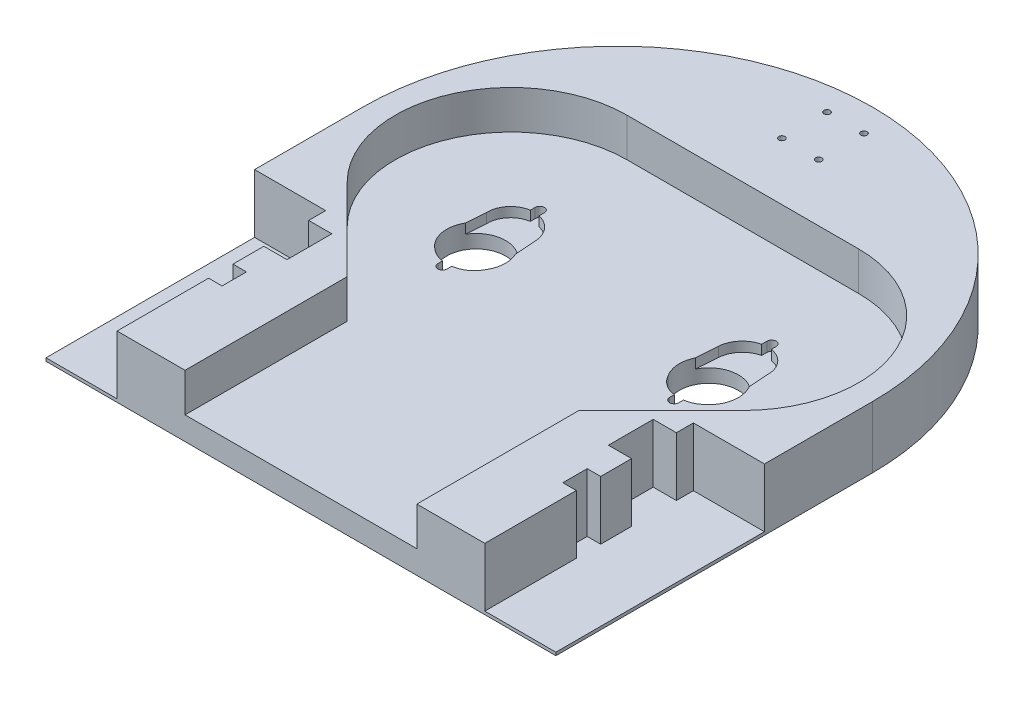
SolidWorks part; units mm, degrees
ref_plane "Plan de face" through (0, 0, 0) normal (0, 0, 1) x (1, 0, 0)
ref_plane "Plan de dessus" through (0, 0, 0) normal (0, 1, 0) x (1, 0, 0)
ref_plane "Plan de droite" through (0, 0, 0) normal (1, 0, 0) x (0, 0, -1)
sketch "Esquisse1" plane through (0, 0, 0) normal (0, 1, 0) x (1, 0, 0)
  line L0 (0, 0) -> (330, 0)
  line L1 (330, 0) -> (330, 370)
  line L2 (0, 0) -> (0, 370)
  line L3 (0, 370) -> (330, 370)
  dimension "D1" = 330
  dimension "D2" = 370
extrude "corp" add sketch "Esquisse1" along normal blind 40
fillet "congé avant" 2 edges at (0, 20, -370) (330, 20, -370) type full round first side face at (0, 20, -185) second side face at (330, 20, -185) middle face at (165, 20, -370)
sketch "Esquisse3" plane through (0, 40, 0) normal (0, 1, 0) x (1, 0, 0)
  line L0 (0, 0) -> (61, 0) construction
  line L1 (0, 0) -> (330, 0) construction
  line L2 (61, 0) -> (61, 135) construction
  line L3 (61, 135) -> (0, 135) construction
  line L4 (0, 205) -> (0, 0) construction
  line L5 (0, 124) -> (46, 124) construction
  line L6 (0, 0) -> (165, 0) construction
  line L7 (330, 0) -> (269, 0) construction
  line L8 (269, 0) -> (269, 135) construction
  line L9 (269, 135) -> (330, 135) construction
  line L10 (330, 0) -> (330, 205) construction
  line L11 (330, 135) -> (330, 0) construction
  line L12 (0, 0) -> (44.9839, 0) construction
  line L13 (0, 135) -> (0, 124) construction
  line L14 (46, 124) -> (46, 135)
  line L15 (46, 124) -> (61, 124)
  line L16 (61, 124) -> (61, 95)
  line L17 (61, 95) -> (46, 95)
  line L18 (46, 95) -> (46, 75) construction
  line L19 (46, 75) -> (54.7242, 75) construction
  line L20 (54.7242, 75) -> (54.7242, 59.2344) construction
  line L21 (54.7242, 59.2344) -> (46, 59.2344) construction
  line L22 (46, 59.2344) -> (46, 0) construction
  line L23 (46, 95) -> (46, 75)
  line L24 (54.7242, 75) -> (54.7242, 59.2344)
  line L25 (54.7242, 59.2344) -> (46, 59.2344)
  line L26 (46, 59.2344) -> (46, 0)
  line L27 (46, 135) -> (0, 135)
  line L28 (0, 135) -> (0, 0)
  line L29 (0, 0) -> (46, 0)
  line L30 (46, 75) -> (54.7242, 75)
  line L31 (165, 0) -> (165, 212.5545) construction
  line L32 (284, 95) -> (284, 75)
  line L33 (269, 95) -> (284, 95)
  line L34 (269, 124) -> (269, 95)
  line L35 (284, 124) -> (269, 124)
  line L36 (284, 124) -> (284, 135)
  line L37 (284, 135) -> (330, 135)
  line L38 (330, 135) -> (330, 0)
  line L39 (330, 0) -> (284, 0)
  line L40 (284, 59.2344) -> (284, 0)
  line L41 (275.2758, 59.2344) -> (284, 59.2344)
  line L42 (275.2758, 75) -> (275.2758, 59.2344)
  line L43 (284, 75) -> (275.2758, 75)
  dimension "D1" = 61
  dimension "D4" = 135
  dimension "D5" = 11
  dimension "D6" = 46
  dimension "D7" = 29
  dimension "D8" = 15
  dimension "D9" = 20
extrude "trou pour roue" cut sketch "Esquisse3" against normal blind 38
sketch "Esquisse4" plane through (0, 40, 0) normal (0, 1, 0) x (1, 0, 0)
  line L0 (330, 0) -> (0, 0) construction
  line L1 (330, 0) -> (165, 0) construction
  line L2 (165, 0) -> (165, 370) construction
  line L3 (330, 370) -> (0, 370) construction
  line L4 (165, 348.436) -> (147.5, 348.436) construction
  line L5 (165, 348.436) -> (182.5, 348.436) construction
  line L6 (182.5, 348.436) -> (182.5, 352.4586) construction
  line L7 (182.5, 352.4586) -> (178.95, 352.4586) construction
  line L8 (176.95, 350.4586) -> (176.95, 337.8086) construction
  circle A0 centre (176.95, 352.4586) radius 2
  circle A1 centre (176.95, 323.1586) radius 2
  circle A2 centre (153.05, 323.1586) radius 2
  circle A3 centre (153.05, 352.4586) radius 2
  dimension "D1" = 330
  dimension "D2" = 17.5
  dimension "D3" = 17.5
  dimension "D4" = 3.55
  dimension "D5" = 2
  dimension "D6" = 12.65
extrude "trou pour roulette" cut sketch "Esquisse4" against normal blind 50
sketch "Esquisse5" plane through (0, 40, 0) normal (0, 1, 0) x (1, 0, 0)
  line L0 (0, 0) -> (165, 0) construction
  line L1 (46, 0) -> (284, 0) construction
  line L2 (165, 0) -> (165, 370) construction
  line L3 (165, 211) -> (240, 211) construction
  line L4 (165, 211) -> (90, 211) construction
  line L5 (90, 286) -> (240, 286)
  line L7 (293.033, 157.967) -> (240, 104.934)
  line L8 (90, 0) -> (90, 104.934)
  line L9 (240, 104.934) -> (240, 0) construction
  line L11 (90, 0) -> (240, 0)
  line L12 (240, 0) -> (240, 104.934)
  line L13 (90, 104.934) -> (36.967, 157.967)
  arc A0 (330, 205) -> (0, 205) centre (165, 205) ccw construction
  arc A3 (240, 286) -> (293.033, 157.967) centre (240, 211) cw
  arc A4 (90, 286) -> (36.967, 157.967) centre (90, 211) ccw
  dimension "D1" = 75
  dimension "D2" = 75
  dimension "D3" = 211
extrude "Trou pour balayeur" cut sketch "Esquisse5" against normal blind 25
sketch "Esquisse6" plane through (0, 15, 0) normal (0, 1, 0) x (1, 0, 0)
  line L0 (0, 0) -> (165, 0) construction
  line L1 (90, 0) -> (240, 0) construction
  line L2 (165, 0) -> (165, 211) construction
  line L3 (165, 211) -> (90, 211) construction
  line L4 (165, 211) -> (240, 211) construction
  line L5 (240, 211) -> (240, 229.6) construction
  line L6 (237, 229.6) -> (237, 226.1784) construction
  line L7 (243, 229.6) -> (243, 226.4491) construction
  line L8 (242.9847, 166.6) -> (242.9847, 169.6685) construction
  line L9 (236.9847, 166.6) -> (236.9847, 169.6756) construction
  line L10 (240, 229.6) -> (240, 169.6) construction
  line L11 (240, 169.6) -> (253.0553, 169.6) construction
  line L12 (255.8858, 211) -> (257.5061, 187.1)
  line L13 (224.1142, 211) -> (222.5061, 187.1)
  line L14 (240, 169.6) -> (239.9847, 166.6) construction
  line L15 (165, 211) -> (165, 370) construction
  line L16 (74.1142, 211) -> (72.4939, 187.1)
  line L17 (105.8858, 211) -> (107.4939, 187.1)
  line L18 (240, 229.6) -> (240, 226.6) construction
  circle A0 centre (240, 229.6) radius 3
  circle A2 centre (239.9847, 166.6) radius 3
  arc A4 (222.5061, 187.1) -> (240, 169.6) centre (238.9025, 185.9968) ccw
  arc A5 (224.1142, 211) -> (240, 226.6) centre (240.8206, 209.8759) cw
  arc A6 (240, 226.6) -> (255.8858, 211) centre (240.7425, 211.4676) cw
  arc A7 (257.5061, 187.1) -> (240, 169.6) centre (241.1168, 185.9889) cw
  arc A8 (330, 205) -> (0, 205) centre (165, 205) ccw construction
  circle A9 centre (90.0153, 166.6) radius 3
  circle A10 centre (90, 229.6) radius 3
  arc A11 (90, 226.6) -> (74.1142, 211) centre (89.2575, 211.4676) ccw
  arc A12 (105.8858, 211) -> (90, 226.6) centre (89.1794, 209.8759) ccw
  arc A13 (107.4939, 187.1) -> (90, 169.6) centre (91.0975, 185.9968) cw
  arc A14 (72.4939, 187.1) -> (90, 169.6) centre (88.8832, 185.9889) ccw
  dimension "D5" = 6
  dimension "D8" = 6
  dimension "D9" = 3
  dimension "D1" = 211
  dimension "D2" = 75
  dimension "D3" = 75
  dimension "D4" = 18.6
  dimension "D6" = 3
  dimension "D7" = 60
extrude "moteur pale" cut sketch "Esquisse6" against normal blind 6.3 contours A7 L12 A6 A0 A5 L13 A4 A2 | L16 A14 A9 A13 L17 A12 A10 A11 region at (240.0684, 15, -197.4408) region at (89.9316, 15, -197.4408)
sketch "Esquisse7" plane through (0, 15, 0) normal (0, 1, 0) x (1, 0, 0)
  line L0 (89.8773, 226.6025) -> (90, 229.6) construction
  line L1 (240.1227, 226.6025) -> (240, 229.6) construction
  arc A0 (89.7547, 226.61) -> (90, 226.6) centre (90, 229.6) ccw construction
  arc A1 (240, 226.6) -> (240.2453, 226.61) centre (240, 229.6) ccw construction
  circle A2 centre (240, 229.6) radius 3
  circle A3 centre (90, 229.6) radius 3
  circle A4 centre (90.0153, 166.6) radius 3
  circle A5 centre (239.9847, 166.6) radius 3
extrude "Enlèv. mat.-Extru.10" cut sketch "Esquisse7" against normal blind 6.3
sketch "Esquisse8" plane through (0, 15, 0) normal (0, 1, 0) x (1, 0, 0)
  line L0 (93, 229.6) -> (93, 226.1784)
  line L1 (87, 229.6) -> (87, 226.4491)
  line L2 (87, 229.6) -> (93, 229.6)
  line L3 (93, 226.1784) -> (87, 226.1784)
  line L4 (87, 226.1784) -> (87, 226.4491)
  line L5 (165, 235.5181) -> (165, 187.1105) construction
  line L6 (165, 211) -> (165, 370) construction
  line L7 (165, 0) -> (165, 211) construction
  line L8 (237, 226.1784) -> (243, 226.1784)
  line L9 (237, 229.6) -> (237, 226.1784)
  line L10 (243, 229.6) -> (237, 229.6)
  line L11 (243, 229.6) -> (243, 226.4491)
  line L12 (243, 226.1784) -> (243, 226.4491)
  line L13 (93.0153, 166.6) -> (93.0153, 169.6756)
  line L14 (93.0153, 166.6) -> (87.0153, 166.6)
  line L15 (87.0153, 166.6) -> (87.0153, 169.6756)
  line L16 (87.0153, 169.6756) -> (93.0153, 169.6756)
  line L17 (242.9847, 166.6) -> (242.9847, 169.6756)
  line L18 (236.9847, 166.6) -> (242.9847, 166.6)
  line L19 (236.9847, 166.6) -> (236.9847, 169.6756)
  line L20 (242.9847, 169.6756) -> (236.9847, 169.6756)
  circle A0 centre (90, 229.6) radius 3 construction
  arc A1 (105.8858, 211) -> (90, 226.6) centre (89.1794, 209.8759) ccw construction
  arc A2 (90, 226.6) -> (74.1142, 211) centre (89.2575, 211.4676) ccw construction
  circle A3 centre (90.0153, 166.6) radius 3 construction
  arc A4 (90, 169.6) -> (107.4939, 187.1) centre (91.0975, 185.9968) ccw construction
extrude "Enlèv. mat.-Extru.11" cut sketch "Esquisse8" against normal blind 6.3
sketch "Esquisse9" plane through (0, 15, 0) normal (0, 1, 0) x (1, 0, 0)
  line L0 (222.469, 185.9968) -> (257.5437, 185.9889) construction
  line L2 (236.9847, 169.6756) -> (239.9861, 169.6756) construction
  line L3 (90, 0) -> (165, 0) construction
  line L4 (90, 0) -> (240, 0) construction
  line L5 (165, 0) -> (165, 276.6198) construction
  arc A0 (222.5061, 187.1) -> (236.9847, 169.6756) centre (238.9025, 185.9968) ccw construction
  arc A1 (222.5061, 187.1) -> (236.9847, 169.6756) centre (238.9025, 185.9968) ccw construction
  arc A2 (242.9847, 169.6685) -> (257.5061, 187.1) centre (241.1168, 185.9889) ccw construction
  arc A3 (242.9847, 169.6685) -> (257.5061, 187.1) centre (241.1168, 185.9889) ccw construction
  circle A6 centre (240.3092, 188.7348) radius 19.062
  circle A7 centre (89.6908, 188.7348) radius 19.062
extrude "Enlèv. mat.-Extru.12" cut sketch "Esquisse9" against normal blind 33
